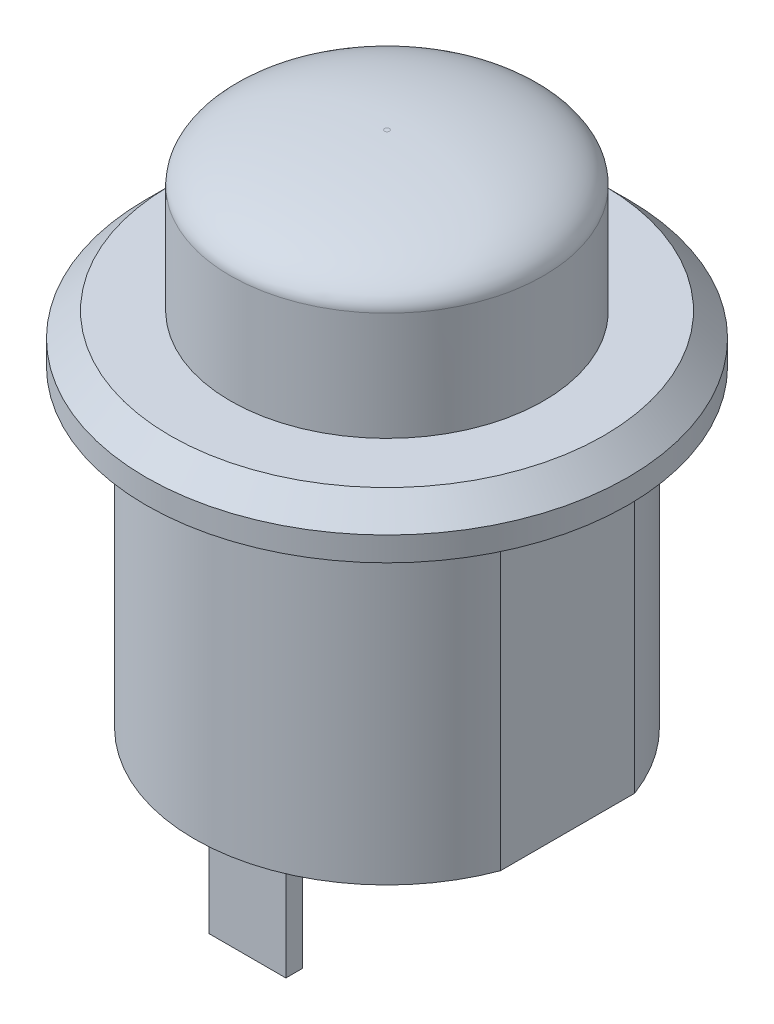
SolidWorks part; units mm, degrees
ref_plane "Front Plane" through (0, 0, 0) normal (0, 0, 1) x (1, 0, 0)
ref_plane "Top Plane" through (0, 0, 0) normal (0, 1, 0) x (1, 0, 0)
ref_plane "Right Plane" through (0, 0, 0) normal (1, 0, 0) x (0, 0, -1)
sketch "Sketch1" plane through (0, 0, 0) normal (0, 1, 0) x (1, 0, 0)
  line L0 (-7.5, 2.7839) -> (-7.5, -2.7839)
  line L1 (7.5, -2.7839) -> (7.5, 2.7839)
  arc A0 (7.5, 2.7839) -> (-7.5, 2.7839) centre (0, 0) ccw
  arc A1 (-7.5, -2.7839) -> (7.5, -2.7839) centre (0, 0) ccw
  point P4 (7.5, 0)
  dimension "D2" = 8
  dimension "D3" = 8
  dimension "D1" = 15
extrude "Boss-Extrude1" add sketch "Sketch1" along normal blind 13
sketch "Sketch2" plane through (0, 13, 0) normal (0, 1, 0) x (1, 0, 0)
  circle A0 centre (0, 0) radius 10
  dimension "D1" = 20
extrude "Boss-Extrude2" add sketch "Sketch2" along normal blind 2
chamfer "Chamfer1" distance 1 angle 45 1 edges at (0, 15, 10)
sketch "Sketch3" plane through (0, 15, 0) normal (0, 1, 0) x (1, 0, 0)
  circle A0 centre (0, 0) radius 6.5
  dimension "D1" = 13
extrude "Boss-Extrude3" add sketch "Sketch3" along normal blind 6.5
fillet "Fillet1" radius 2 1 edges at (0, 21.5, 6.5) second distance 6.4 first distance on face at (0, 21.5, 6.5)
sketch "Sketch4" plane through (0, 0, 0) normal (0, -1, 0) x (1, 0, 0)
  line L0 (11, 0) -> (-11, 0) construction
  line L1 (-1.6, 5.8) -> (1.6, 5.8)
  line L2 (-1.6, 5.8) -> (-1.6, 5.1)
  line L3 (-1.6, 5.1) -> (1.6, 5.1)
  line L4 (1.6, 5.8) -> (1.6, 5.1)
  line L5 (-1.6, -5.1) -> (1.6, -5.1)
  line L6 (-1.6, -5.1) -> (-1.6, -5.8)
  line L7 (-1.6, -5.8) -> (1.6, -5.8)
  line L8 (1.6, -5.1) -> (1.6, -5.8)
  line L9 (0, -11) -> (0, 11) construction
  point P10 (0, -5.1)
  dimension "D1" = 0.7
  dimension "D2" = 0.7
  dimension "D3" = 3.2
  dimension "D4" = 3.2
  dimension "D5" = 10.2
  dimension "D6" = 5.1
extrude "Boss-Extrude4" add sketch "Sketch4" along normal blind 5.3
